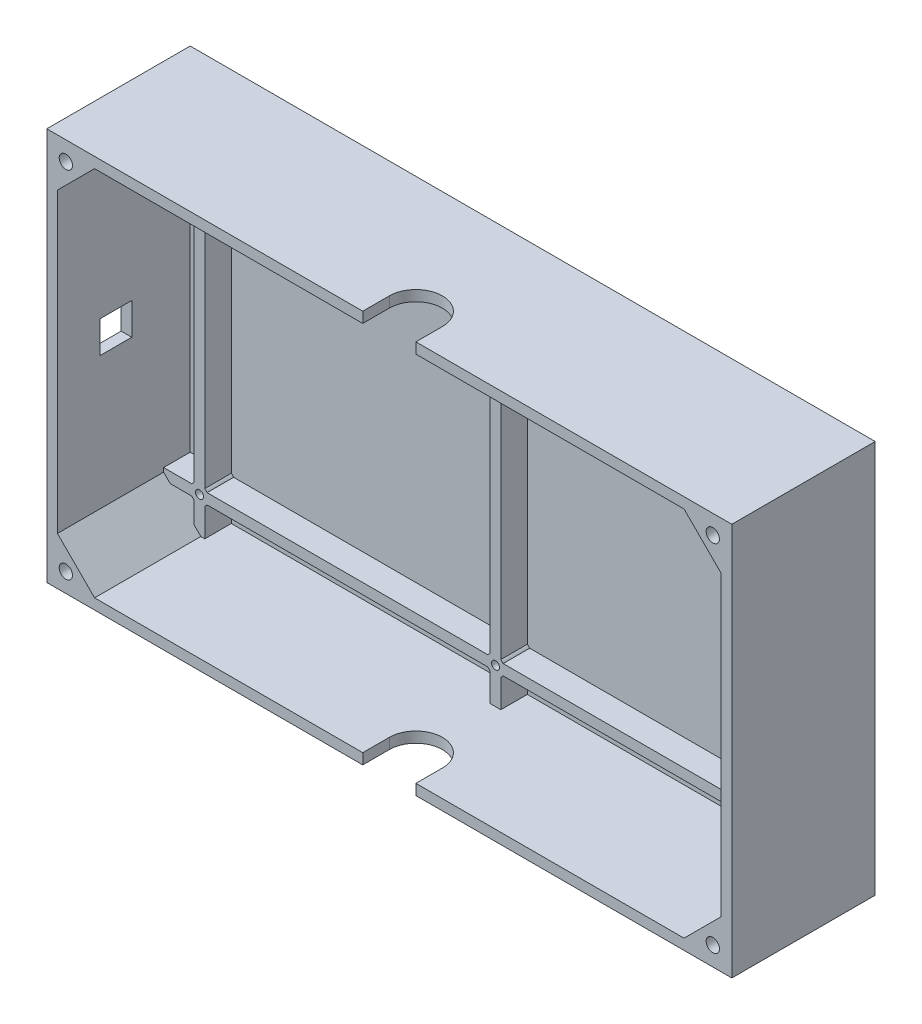
SolidWorks part; units mm, degrees
ref_plane "Plan de face" through (0, 0, 0) normal (0, 0, 1) x (1, 0, 0)
ref_plane "Plan de dessus" through (0, 0, 0) normal (0, 1, 0) x (1, 0, 0)
ref_plane "Plan de droite" through (0, 0, 0) normal (1, 0, 0) x (0, 0, -1)
sketch "Esquisse1" plane through (0, 0, 0) normal (0, 0, 1) x (1, 0, 0)
  line L1 (-125, -70) -> (-111, -70) construction
  line L2 (0, -55) -> (0, 55) construction
  line L3 (-111, 70) -> (111, 70)
  line L4 (55, 0) -> (-55, 0) construction
  line L5 (-125, 70) -> (-111, 70) construction
  line L6 (-129, -74) -> (129, -74)
  line L7 (129, 74) -> (129, -74)
  line L8 (-129, 74) -> (129, 74)
  line L9 (-129, 74) -> (-129, -74)
  line L10 (-115, 60) -> (-115, -60) construction
  line L11 (-115, -60) -> (115, -60) construction
  line L12 (115, 60) -> (115, -60) construction
  line L13 (-115, 60) -> (115, 60) construction
  line L14 (-111, 70) -> (-125, 56)
  line L15 (-111, -70) -> (-125, -56)
  line L16 (111, 70) -> (125, 56)
  line L17 (111, -70) -> (125, -56)
  line L18 (-129, 74) -> (-118, 63) construction
  line L19 (-129, 74) -> (-118, 63) construction
  line L20 (-125, 56) -> (-125, -56)
  line L21 (-125, 70) -> (-125, -70) construction
  line L22 (125, 56) -> (125, -56)
  line L23 (125, 70) -> (125, -70) construction
  line L24 (115, -60) -> (111.5, -60) construction
  line L25 (-125, 70) -> (125, 70) construction
  line L26 (111.5, -60) -> (111.5, -56.5) construction
  line L27 (111, -70) -> (125, -70) construction
  line L28 (-125, -70) -> (125, -70) construction
  line L29 (-111, -70) -> (111, -70)
  line L30 (-111.5, -56.5) -> (-111.5, -69.5) construction
  line L31 (-113.5, 67.5) -> (-113.5, -67.5) construction
  line L32 (-113.5, -59.3723) -> (-113.5, -67.5)
  line L33 (-113.5, -56.5) -> (-113.5, -69.5) construction
  line L34 (-109.5, 70) -> (-109.5, -59.3723) construction
  line L35 (-109.5, -59.3723) -> (-109.5, -70)
  line L36 (-109.5, 70) -> (-109.5, 59.3723)
  line L37 (-113.5, 67.5) -> (-113.5, 59.3723)
  line L38 (-113.5, 53.6277) -> (-113.5, -53.6277)
  line L39 (-109.5, -53.6277) -> (-109.5, 53.6277)
  line L40 (-108.6277, 58.5) -> (-2.8723, 58.5)
  line L41 (108.6277, 54.5) -> (2.8723, 54.5)
  line L42 (-125, 54.5) -> (-114.3723, 54.5)
  line L43 (-122.5, 58.5) -> (-114.3723, 58.5)
  line L44 (-111.5, 56.5) -> (111.5, 56.5) construction
  line L45 (-2.8723, 58.5) -> (2.8723, 58.5) construction
  line L46 (-2.8723, 54.5) -> (-108.6277, 54.5)
  line L47 (2.8723, 54.5) -> (-2.8723, 54.5) construction
  line L48 (2.8723, 58.5) -> (108.6277, 58.5)
  line L49 (113.5, 53.6277) -> (113.5, -53.6277)
  line L50 (109.5, -53.6277) -> (109.5, 53.6277)
  line L51 (108.6277, -54.5) -> (2.8723, -54.5)
  line L52 (2.8723, -58.5) -> (108.6277, -58.5)
  line L53 (-108.6277, -58.5) -> (-2.8723, -58.5)
  line L54 (-2.8723, -54.5) -> (-108.6277, -54.5)
  line L55 (0, -56.5) -> (0, 56.5) construction
  line L56 (2, -70) -> (2, 70) construction
  line L57 (2, -56.5) -> (2, 56.5) construction
  line L58 (2, -59.3723) -> (2, -70)
  line L59 (2, -53.6277) -> (2, 53.6277)
  line L60 (2, 70) -> (2, 59.3723)
  line L61 (-2, -59.3723) -> (-2, -70)
  line L62 (-2, -53.6277) -> (-2, 53.6277)
  line L63 (-2, 70) -> (-2, 59.3723)
  line L64 (-125, -54.5) -> (-114.3723, -54.5)
  line L65 (-122.5, -58.5) -> (-114.3723, -58.5)
  line L66 (125, -54.5) -> (114.3723, -54.5)
  line L67 (122.5, -58.5) -> (114.3723, -58.5)
  line L68 (109.5, -59.3723) -> (109.5, -70)
  line L69 (113.5, -59.3723) -> (113.5, -67.5)
  line L70 (125, 54.5) -> (114.3723, 54.5)
  line L71 (122.5, 58.5) -> (114.3723, 58.5)
  line L72 (113.5, 67.5) -> (113.5, 59.3723)
  line L73 (109.5, 70) -> (109.5, 59.3723)
  circle A0 centre (-121.8321, 66.8321) radius 2.5
  circle A1 centre (-121.8321, -66.8321) radius 2.5
  circle A2 centre (121.8321, -66.8321) radius 2.5
  circle A3 centre (121.8321, 66.8321) radius 2.5
  circle A4 centre (111.5, -56.5) radius 1.5
  circle A5 centre (111.5, 56.5) radius 1.5
  circle A6 centre (-111.5, -56.5) radius 1.5
  circle A7 centre (-111.5, 56.5) radius 1.5
  circle A8 centre (-111.5, 56.5) radius 3.5
  circle A9 centre (111.5, 56.5) radius 3.5
  circle A10 centre (-111.5, -56.5) radius 3.5
  circle A11 centre (111.5, -56.5) radius 3.5
  circle A12 centre (0, 56.5) radius 3.5
  circle A13 centre (0, 56.5) radius 1.5
  arc A14 (2.8723, -54.5) -> (2.8596, -58.518) centre (0, -56.5) cw
  circle A15 centre (0, -56.5) radius 1.5
  arc A16 (2.8596, -58.518) -> (2.8723, -54.5) centre (0, -56.5) cw
  point P16 (-125, 56)
  point P17 (-111, 70)
  point P53 (-113.5, -67.5)
  point P54 (-113.5, -59.3723)
  point P61 (-109.5, -59.3723)
  point P67 (0, 56.5)
  point P79 (-2.8723, 58.5)
  point P80 (-2.8723, 54.5)
  point P81 (2.8723, 58.5)
  point P82 (2.8723, 54.5)
  dimension "D11" = 2
  dimension "D12" = 7
  dimension "D13" = 2
  dimension "D14" = 3
  dimension "D1" = 140
  dimension "D2" = 250
  dimension "D4" = 14
  dimension "D5" = 120
  dimension "D6" = 230
  dimension "D7" = 14
  dimension "D9" = 3.5
  dimension "D10" = 3.5
  dimension "D15" = 2
  dimension "D3" = 4
extrude "Boss.-Extru.2" add sketch "Esquisse1" along normal blind 10 contours L8 L9 L6 L7 A1 A0 L29 L15 L20 L14 L3 L16 L22 L17 A2 A3 | A12 L60 L3 L63 | A12 L41 A9 L48 | L62 A16 L59 A12 | A12 L40 A8 L46 | A12 A13 | L71 A9 L70 L22 L16 | A9 A5 | L73 A9 L72 L16 L3 | A11 L49 A9 L50 | L51 A16 A14 L52 A11 | A11 A4 | A11 L67 L17 L22 L66 | A11 L68 L29 L17 L69 | L58 A16 L61 L29 | A16 A14 A15 | L53 A16 L54 A10 | L35 A10 L32 L15 L29 | L65 A10 L64 L20 L15 | L38 A10 L39 A8 | A10 A6 | A8 L36 L3 L14 L37 | A8 L43 L14 L20 L42 | A8 A7 region at (-111.4032, 64.5437, 0) region at (0, 64.8978, 0) region at (-109.0951, 58.9049, 0) region at (-119.5437, 56.4032, 0) region at (0, 59.901, 0) region at (-55.75, 56.5, 0) region at (111.4032, 64.5437, 0) region at (111.5, 59.901, 0) region at (55.75, 56.5, 0) region at (-119.5437, -56.4032, 0) region at (-111.5, 0, 0) region at (0, 0, 0) region at (-113.9049, -54.0951, 0) region at (119.5437, 56.4032, 0) region at (0, -53.099, 0) region at (111.5, 0, 0) region at (-55.75, -56.5, 0) region at (-111.4032, -64.5437, 0) region at (111.5, -53.099, 0) region at (55.75, -56.5, 0) region at (119.5437, -56.4032, 0) region at (0, -64.8978, 0) region at (111.4032, -64.5437, 0) region at (-126.0256, 0, 0)
extrude "Boss.-Extru.3" add sketch "Esquisse1<5>" against normal blind 4 contours L72 A9 L71 L16 | A12 L48 A9 L73 L3 L60 | A5 | A9 A5 | L71 A9 L70 L22 L16 | A12 L41 A9 L48 | A11 L66 L22 L70 A9 L49 | A11 L49 A9 L50 | L59 A16 L51 A11 L50 A9 L41 A12 | A12 L60 L3 L63 | A12 L63 L3 L36 A8 L40 | A7 | A8 A7 | A8 L36 L3 L14 L37 | L64 A10 L38 A8 L42 L20 | L54 A16 L62 A12 L46 A8 L39 A10 | A12 L40 A8 L46 | L62 A16 L59 A12 | A12 A13 | A0 | A3 | L73 A9 L72 L16 L3 | L51 A16 A14 L52 A11 | A11 L67 L17 L22 L66 | A11 L69 L17 L67 | A11 L68 L29 L17 L69 | A14 A16 L58 L29 L68 A11 L52 | A4 | A11 A4 | A8 L43 L14 L20 L42 | A8 L37 L14 L43 | L38 A10 L39 A8 | L65 A10 L64 L20 L15 | L32 A10 L65 L15 | L61 A16 L53 A10 L35 L29 | L53 A16 L54 A10 | L35 A10 L32 L15 L29 | A6 | A10 A6 | L58 A16 L61 L29 | A15 | A16 A14 A15 | L8 L9 L6 L7 A1 A0 L29 L15 L20 L14 L3 L16 L22 L17 A2 A3 | A2 | A13 | A1 region at (-111.4032, 64.5437, 0) region at (-55.75, 64.2537, 0) region at (-116.5286, 61.5286, 0) region at (0, 64.8978, 0) region at (-109.0951, 58.9049, 0) region at (-119.5437, 56.4032, 0) region at (55.75, 64.2537, 0) region at (0, 59.901, 0) region at (-55.75, 56.5, 0) region at (111.4032, 64.5437, 0) region at (-119.2537, 0, 0) region at (111.5, 59.901, 0) region at (55.75, 56.5, 0) region at (-55.75, 0, 0) region at (-119.5437, -56.4032, 0) region at (-111.5, 0, 0) region at (116.5286, 61.5286, 0) region at (0, 0, 0) region at (-113.9049, -54.0951, 0) region at (119.5437, 56.4032, 0) region at (55.75, 0, 0) region at (0, -53.099, 0) region at (-116.5286, -61.5286, 0) region at (111.5, 0, 0) region at (-55.75, -56.5, 0) region at (-111.4032, -64.5437, 0) region at (119.2537, 0, 0) region at (111.5, -53.099, 0) region at (-55.75, -64.2537, 0) region at (55.75, -56.5, 0) region at (119.5437, -56.4032, 0) region at (0, -64.8978, 0) region at (55.75, -64.2537, 0) region at (116.5286, -61.5286, 0) region at (111.4032, -64.5437, 0) region at (-126.0256, 0, 0) region at (-121.8321, 66.8321, 0) region at (-121.8321, -66.8321, 0) region at (121.8321, -66.8321, 0) region at (121.8321, 66.8321, 0) region at (111.5, -56.5, 0) region at (111.5, 56.5, 0) region at (-111.5, -56.5, 0) region at (-111.5, 56.5, 0) region at (0, 56.5, 0) region at (0, -56.5, 0)
sketch "Esquisse1<5>" plane through (0, 0, 0) normal (0, 0, 1) x (1, 0, 0) same geometry as "Esquisse1"
sketch "Esquisse2" plane through (0, 0, 10) normal (0, 0, 1) x (1, 0, 0)
  line L0 (-125.0431, -70) -> (-111, -70) construction
  line L1 (-111, 70) -> (111, 70)
  line L2 (-125, 70) -> (-111, 70) construction
  line L3 (-129, -74) -> (129, -74)
  line L4 (129, 74) -> (129, -74)
  line L5 (-129, 74) -> (129, 74)
  line L6 (-129, 74) -> (-129, -74)
  line L11 (-111, 70) -> (-125, 56)
  line L12 (-111, -70) -> (-125, -56)
  line L13 (111, 70) -> (125, 56)
  line L14 (111, -70) -> (125, -56)
  line L15 (-129, 74) -> (-118, 63) construction
  line L16 (-129, 74) -> (-118, 63) construction
  line L17 (-125, 56) -> (-125, -56)
  line L18 (125, 56) -> (125, -56)
  line L19 (2, 70) -> (109.5, 70) construction
  line L20 (-113.5, 67.5) -> (-122.5, 58.5) construction
  line L21 (111, -70) -> (124.9569, -70) construction
  line L22 (-111, -70) -> (111, -70)
  line L23 (-125, 54.5) -> (-125, -54.5) construction
  line L24 (-113.5, -67.5) -> (-122.5, -58.5) construction
  line L25 (-109.5, -70) -> (-2, -70) construction
  line L26 (113.5, -67.5) -> (122.5, -58.5) construction
  line L27 (125, 54.5) -> (125, -54.5) construction
  line L28 (113.5, 67.5) -> (122.5, 58.5) construction
  circle A0 centre (-121.8321, 66.8321) radius 2.5
  circle A1 centre (-121.8321, -66.8321) radius 2.5
  circle A2 centre (121.8321, -66.8321) radius 2.5
  circle A3 centre (121.8321, 66.8321) radius 2.5
  circle A4 centre (-121.8321, 66.8321) radius 2.5 construction
  point P11 (-125, 56)
  point P12 (-111, 70)
extrude "Boss.-Extru.5" add sketch "Esquisse2" along normal blind 40
sketch "Esquisse3" plane through (0, 0, 50) normal (0, 0, 1) x (1, 0, 0)
  line L0 (-125.0431, -70) -> (-111, -70) construction
  line L1 (-111, 70) -> (111, 70)
  line L2 (-125, 70) -> (-111, 70) construction
  line L3 (-129, -74) -> (129, -74)
  line L4 (129, 74) -> (129, -74)
  line L5 (-129, 74) -> (129, 74)
  line L6 (-129, 74) -> (-129, -74)
  line L7 (-111, 70) -> (-125, 56)
  line L8 (-111, -70) -> (-125, -56)
  line L9 (111, 70) -> (125, 56)
  line L10 (111, -70) -> (125, -56)
  line L11 (-129, 74) -> (-118, 63) construction
  line L12 (-129, 74) -> (-118, 63) construction
  line L13 (-125, 56) -> (-125, -56)
  line L14 (125, 56) -> (125, -56)
  line L15 (111, -70) -> (124.9569, -70) construction
  line L16 (-111, -70) -> (111, -70)
  circle A0 centre (-121.8321, 66.8321) radius 2.5
  circle A1 centre (-121.8321, -66.8321) radius 2.5
  circle A2 centre (121.8321, -66.8321) radius 2.5
  circle A3 centre (121.8321, 66.8321) radius 2.5
  point P11 (-125, 56)
  point P12 (-111, 70)
sketch "Esquisse4" plane through (-125, 0, 0) normal (1, 0, 0) x (0, 0, -1)
  line L0 (-10, -56) -> (-22, -56) construction
  line L1 (-50, -56) -> (-10, -56) construction
  line L2 (-22, -56) -> (-34, -56) construction
  line L3 (-22, -56) -> (-22, 56) construction
  line L4 (-50, 56) -> (-10, 56) construction
  line L5 (-22, 6) -> (-22, -6)
  line L6 (-22, -6) -> (-34, -6)
  line L7 (-34, -6) -> (-34, 6)
  line L8 (55, 0) -> (-55, 0) construction
  line L9 (-22, 6) -> (-34, 6)
  point P19 (-22, 0)
  point P20 (-34, 0)
  dimension "D1" = 12
  dimension "D2" = 24
  dimension "D3" = 6
extrude "Enlèv. mat.-Extru.1" cut sketch "Esquisse4" against normal up to next
sketch "Esquisse6" plane through (0, -70, 0) normal (0, 1, 0) x (1, 0, 0)
  line L0 (0, -50) -> (0, -40) construction
  line L1 (-111, -50) -> (111, -50) construction
  line L2 (10, -40) -> (10, -50)
  line L3 (10, -50) -> (-10, -50)
  line L4 (-10, -50) -> (-10, -40)
  arc A0 (-10, -40) -> (10, -40) centre (0, -40) cw
  dimension "D2" = 10
  dimension "D1" = 10
extrude "Enlèv. mat.-Extru.2" cut sketch "Esquisse6" against normal up to next
sketch "Esquisse9" plane through (0, 70, 0) normal (0, -1, 0) x (1, 0, 0)
  line L0 (0, 50) -> (0, 40) construction
  line L1 (-111, 50) -> (111, 50) construction
  line L2 (-10, 40) -> (-10, 50)
  line L3 (-10, 50) -> (10, 50)
  line L4 (10, 40) -> (10, 50)
  arc A0 (10, 40) -> (-10, 40) centre (0, 40) cw
  dimension "D2" = 10
  dimension "D1" = 10
extrude "Enlèv. mat.-Extru.3" cut sketch "Esquisse9" against normal up to next
